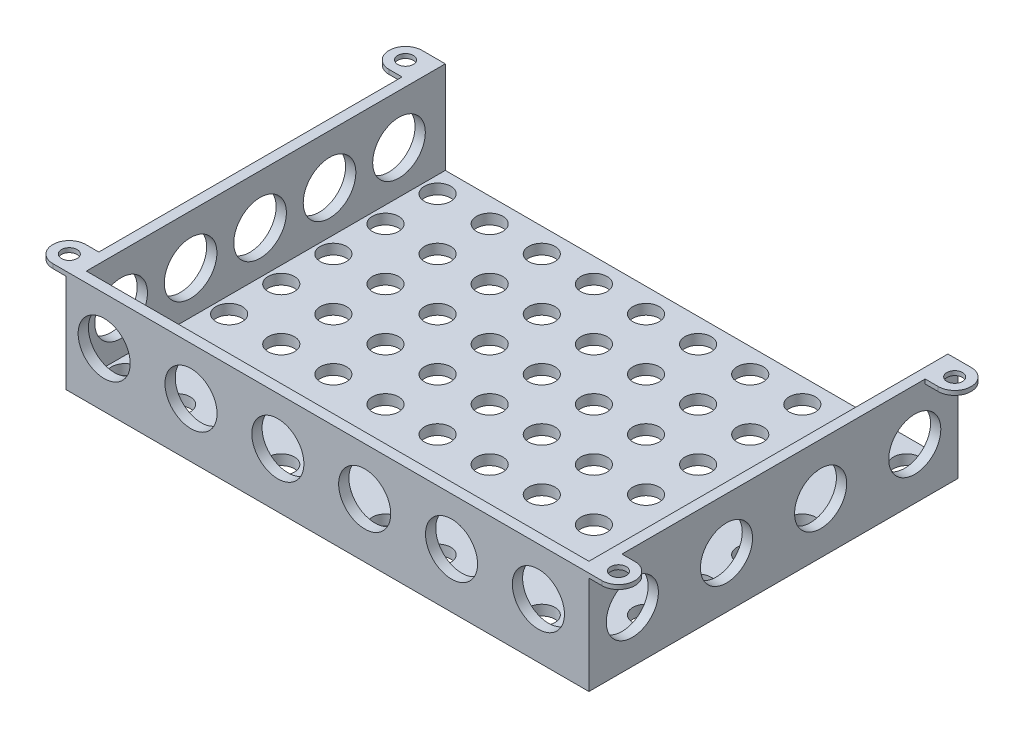
SolidWorks part; units mm, degrees
other "Markup2"
sketch "Sketch32" plane through (-159.4724, 0, 108) normal (-0.262, -0.0774, 0.962) x (0.8638, -0.4632, 0.198)
ref_plane "Front Plane" through (0, 0, 0) normal (0, 0, 1) x (1, 0, 0)
ref_plane "Top Plane" through (0, 0, 0) normal (0, 1, 0) x (1, 0, 0)
ref_plane "Right Plane" through (0, 0, 0) normal (1, 0, 0) x (0, 0, -1)
sketch "Sketch1" plane through (0, 0, 0) normal (0, 1, 0) x (1, 0, 0)
  line L1 (0, 0) -> (-153, 0)
  line L2 (0, 0) -> (0, -108)
  line L3 (0, -108) -> (-153, -108)
  line L4 (-153, 0) -> (-153, -108)
extrude "Boss-Extrude1" add sketch "Sketch1" along normal blind 30 contours L1 L4 L3 L2
shell "Shell1" thickness 3 removed face at (-76.5, 30, 54)
sketch "Sketch7" plane through (0, 30, 0) normal (0, 1, 0) x (1, 0, 0)
  line L0 (-156.81, 0) -> (-153, 0)
  line L1 (-153, 0) -> (-153, -9.652)
  line L2 (-153, 0) -> (-153, -108) construction
  line L3 (-153, -9.652) -> (-156.81, -9.652)
  circle A0 centre (-156.81, -4.826) radius 2.286
  arc A2 (-156.81, 0) -> (-156.81, -9.652) centre (-156.81, -4.826) ccw
  dimension "D1" = 2.54
  dimension "D3" = 4.572
  dimension "D2" = 3.81
extrude "Boss-Extrude7" add sketch "Sketch7" against normal blind 1.27
sketch "Sketch24" plane through (0, 0, 0) normal (0, -1, 0) x (1, 0, 0)
  circle A0 centre (-8.0557, 7.0511) radius 3.8453
extrude "Cut-Extrude8" cut sketch "Sketch24" against normal blind 25.4
pattern_linear "LPattern5" count 10 spacing 15.24 along (-1, 0, 0) of "Cut-Extrude8"
pattern_linear "LPattern6" count 10 spacing 15.24 along (0, 0, 1) of "LPattern5"
sketch "Sketch27" plane through (0, 0, 3) normal (0, 0, 1) x (1, 0, 0)
  line L0 (-3, 3) -> (-3, 30)
  line L1 (-3, 30) -> (-3, 3) construction
  line L2 (-3, 30) -> (-150, 30)
  line L3 (-150, 30) -> (-150, 3)
  line L4 (-150, 3) -> (-3, 3)
extrude "Cut-Extrude10" cut sketch "Sketch27" against normal blind 5.08
sketch "Sketch28" plane through (-153, 0, 0) normal (-1, 0, 0) x (0, 0, 1)
  circle A0 centre (94.8273, 15.5402) radius 7.6982
extrude "Cut-Extrude11" cut sketch "Sketch28" against normal blind 10.16
pattern_linear "LPattern7" count 5 spacing 20.32 along (0, 0, -1) of "Cut-Extrude11"
sketch "Sketch29" plane through (0, 0, 108) normal (0, 0, 1) x (1, 0, 0)
  circle A0 centre (-14.7838, 16.0027) radius 7.62
  dimension "D1" = 15.24
extrude "Cut-Extrude13" cut sketch "Sketch29" against normal blind 7.62 contours A0
pattern_linear "LPattern9" count 6 spacing 25.4 along (-1, 0, 0) of "Cut-Extrude13"
sketch "Sketch30" plane through (0, 0, 0) normal (1, 0, 0) x (0, 0, -1)
  line L0 (0, 30) -> (0, 0) construction
  line L1 (-108, 30) -> (-108, 0) construction
  circle A0 centre (-12.7, 15) radius 7.62
  circle A1 centre (-40.2333, 15) radius 7.62
  circle A2 centre (-67.7667, 15) radius 7.62
  circle A3 centre (-95.3, 15) radius 7.62
  point P13 (0, 15)
  dimension "D2" = 15.24
  dimension "D3" = 12.7
  dimension "D4" = 12.7
  dimension "D1" = 4
extrude "Cut-Extrude14" cut sketch "Sketch30" against normal blind 7.62
ref_plane "Plane1" through (0, 0, 54) normal (0, 0, -1) x (-1, 0, 0)
ref_plane "Plane2" through (-76.5, 0, 0) normal (-1, 0, 0) x (0, 0, 1)
mirror "Mirror1" about plane through (0, 0, 54) normal (0, 0, -1) of "Boss-Extrude7"
mirror "Mirror2" about plane through (-76.5, 0, 0) normal (-1, 0, 0) of "Mirror1"
